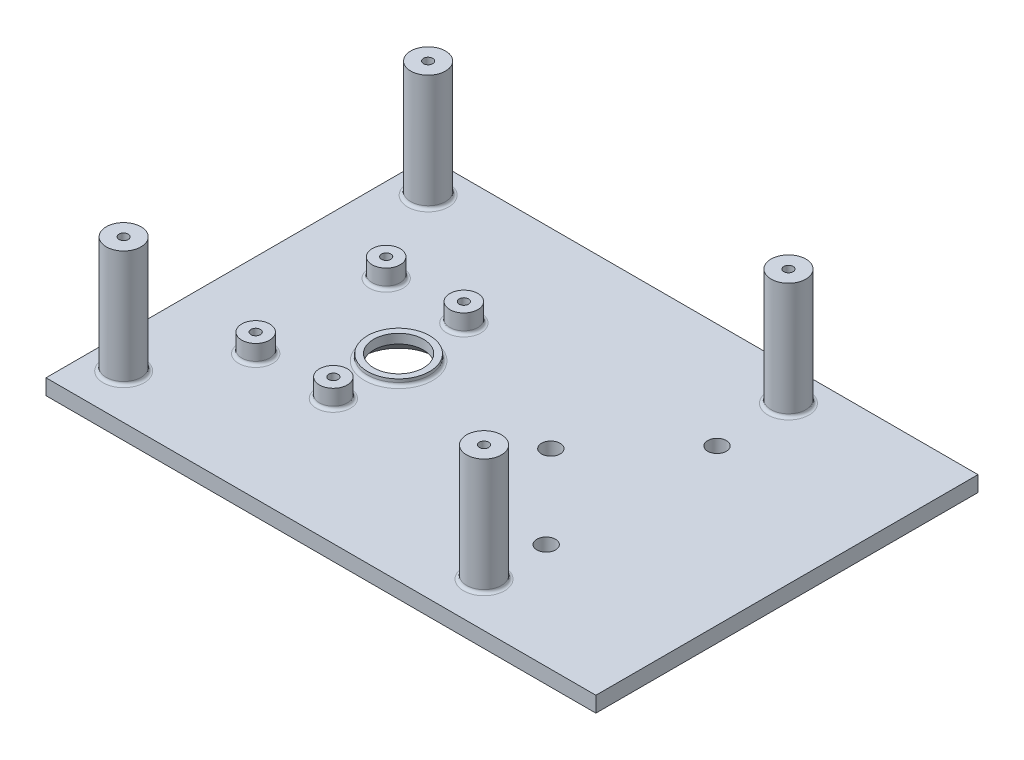
SolidWorks part; units mm, degrees
ref_plane "Front Plane" through (0, 0, 0) normal (0, 0, 1) x (1, 0, 0)
ref_plane "Top Plane" through (0, 0, 0) normal (0, 1, 0) x (1, 0, 0)
ref_plane "Right Plane" through (0, 0, 0) normal (1, 0, 0) x (0, 0, -1)
sketch "Sketch1" plane through (0, 0, 0) normal (0, 1, 0) x (1, 0, 0)
  line L1 (-44.25, 61.5) -> (44.25, 61.5)
  line L2 (-44.25, 61.5) -> (-44.25, 0)
  line L3 (-44.25, 0) -> (44.25, 0)
  line L4 (44.25, 61.5) -> (44.25, 0)
  circle A0 centre (-38.95, 56.2) radius 2.8
  circle A1 centre (-38.95, 7.2) radius 2.8
  circle A2 centre (19.05, 7.2) radius 2.8
  circle A3 centre (19.05, 56.2) radius 2.8
  circle A8 centre (19.05, 7.2) radius 1.4 construction
  point P5 (0, 0)
  dimension "D3" = 5.6
  dimension "D1" = 88.5
  dimension "D2" = 61.5
  dimension "D5" = 58
  dimension "D6" = 49
extrude "Boss-Extrude1" add sketch "Sketch1" along normal blind 2.5 contours L2 L3 L4 L1
extrude "Boss-Extrude2" add sketch "Sketch1<3>" along normal blind 21.2 contours A1 | A0 | A3 | A2
sketch "Sketch1<3>" plane through (0, 0, 0) normal (0, 1, 0) x (1, 0, 0) same geometry as "Sketch1"
sketch "Sketch3" plane through (0, 2.5, 0) normal (0, 1, 0) x (1, 0, 0)
  line L0 (-44.25, 61.5) -> (-44.25, 0) construction
  circle A0 centre (-18.25, 30.75) radius 4
  circle A1 centre (-18.25, 30.75) radius 5
  circle A2 centre (-18.25, 41.25) radius 0.75
  circle A3 centre (-18.25, 41.25) radius 2.25
  circle A4 centre (-18.25, 20.25) radius 0.75
  circle A5 centre (-18.25, 20.25) radius 2.25
  circle A6 centre (-30.75, 41.25) radius 0.75
  circle A7 centre (-30.75, 41.25) radius 2.25
  circle A8 centre (-30.75, 20.25) radius 0.75
  circle A9 centre (-30.75, 20.25) radius 2.25
  point P5 (-44.25, 30.75)
  dimension "D1" = 8
  dimension "D3" = 10
  dimension "D4" = 1.5
  dimension "D5" = 4.5
  dimension "D2" = 26
  dimension "D6" = 21
  dimension "D7" = 12.5
  dimension "D8" = 10.5
extrude "Boss-Extrude3" add sketch "Sketch3" along normal blind 1 contours A1 | A0
extrude "Boss-Extrude4" add sketch "Sketch3<4>" along normal blind 3 contours A5 | A4 | A7 | A6 | A3 | A2 | A8 | A9
sketch "Sketch3<4>" plane through (0, 2.5, 0) normal (0, 1, 0) x (1, 0, 0) same geometry as "Sketch3"
extrude "Cut-Extrude3" cut sketch "Sketch3<5>" against normal blind 10 contours A0
sketch "Sketch3<5>" plane through (0, 2.5, 0) normal (0, 1, 0) x (1, 0, 0) same geometry as "Sketch3"
chamfer "Chamfer1" distance 2 angle 45 1 edges at (-18.25, 0, -34.75)
sketch "Sketch4" plane through (0, 21.2, 0) normal (0, 1, 0) x (1, 0, 0)
  circle A0 centre (-38.95, 56.2) radius 0.75
  circle A1 centre (19.05, 56.2) radius 0.75
  circle A2 centre (-38.95, 7.2) radius 0.75
  circle A3 centre (19.05, 7.2) radius 0.75
  dimension "D1" = 1.5
extrude "Cut-Extrude4" cut sketch "Sketch4" against normal blind 5
fillet "Fillet1" radius 0.5 9 edges at (-30.75, 2.5, -43.5) (-18.25, 2.5, -35.75) (-30.75, 2.5, -22.5) (-18.25, 2.5, -22.5) (-18.25, 2.5, -43.5) (-38.95, 2.5, -10) (-38.95, 2.5, -59) (19.05, 2.5, -10) (19.05, 2.5, -59)
hole_wizard "Ø3.0mm Dowel Hole1" positions "Sketch5" profile "Sketch7" hole size "Ø3.0" standard "ANSI Metric" end condition up to next
sketch "Sketch5" plane through (0, 0, 0) normal (0, -1, 0) x (-1, 0, 0)
  line L0 (44.25, 61.5) -> (-44.25, 61.5) construction
  line L1 (44.25, 0) -> (-44.25, 0) construction
  line L2 (-44.25, 61.5) -> (-44.25, 0) construction
  point P0 (-19.25, 44.5)
  point P2 (-19.25, 17)
  point P5 (-6.25, 30.75)
  point P12 (0, 0)
  point P13 (0, 0)
  dimension "D1" = 17
  dimension "D2" = 17
  dimension "D3" = 13
  dimension "D4" = 27.5
  dimension "D5" = 13.75
  dimension "D6" = 25
sketch "Sketch7" plane through (19.25, 0, -44.5) normal (1, 0, 0) x (0, 0, -1)
  line L0 (0, 0) -> (0, 2.5)
  line L1 (0, 2.5) -> (1.5, 2.5)
  line L2 (1.5, 2.5) -> (1.5, 0)
  line L5 (1.5, 0) -> (0, 0)
  line L11 (0, -6.35) -> (0, 107.95) construction
  dimension "Thru Hole Dia." = 3
  dimension "Thru Hole Depth" = 2.5
